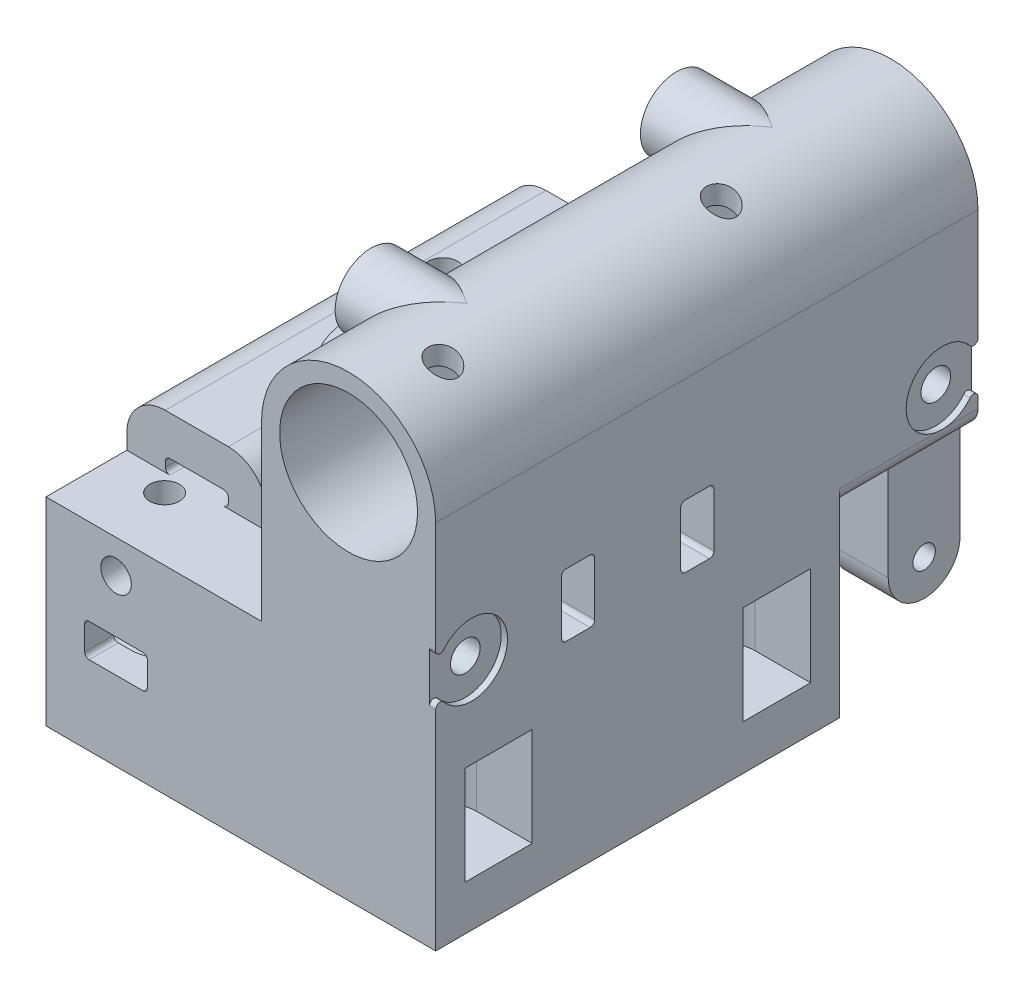
SolidWorks part; units mm, degrees
ref_plane "Front Plane" through (0, 0, 0) normal (0, 0, 1) x (1, 0, 0)
ref_plane "Top Plane" through (0, 0, 0) normal (0, 1, 0) x (1, 0, 0)
ref_plane "Right Plane" through (0, 0, 0) normal (1, 0, 0) x (0, 0, -1)
sketch "Sketch1" plane through (0, 0, 0) normal (0, 0, 1) x (1, 0, 0)
  line L57 (9.7, 0) -> (9.7, -41.3)
  line L58 (-9.7, -19.2) -> (-18.1, -19.2)
  line L61 (-29.4, -32) -> (-29.4, -29.3)
  line L62 (-29.4, -18.1) -> (-29.4, -18.7)
  line L63 (-28.9, -19.2) -> (-22.9, -19.2)
  line L64 (-22.4, -18.7) -> (-22.4, -18.1)
  line L65 (-22.9, -17.6) -> (-28.9, -17.6)
  line L66 (-28.9, -32.5) -> (-22.9, -32.5)
  line L67 (-22.4, -32) -> (-22.4, -29.3)
  line L68 (-28.9, -28.8) -> (-22.9, -28.8)
  line L76 (-9.7, -19.2) -> (-9.7, 0)
  line L77 (9.7, -41.3) -> (-33.7, -41.3)
  line L80 (-33.7, -41.3) -> (-33.7, -17.49)
  line L81 (-29.41, -13.2) -> (-22.39, -13.2)
  line L82 (-18.1, -17.49) -> (-18.1, -19.2)
  circle A0 centre (0, 0) radius 7.68
  arc A39 (9.7, 0) -> (-9.7, 0) centre (0, 0) ccw
  circle A59 centre (-25.9, -22.91) radius 1.7
  arc A60 (-28.9, -17.6) -> (-29.4, -18.1) centre (-28.9, -18.1) ccw
  arc A61 (-29.4, -18.7) -> (-28.9, -19.2) centre (-28.9, -18.7) ccw
  arc A62 (-22.9, -19.2) -> (-22.4, -18.7) centre (-22.9, -18.7) ccw
  arc A63 (-22.4, -18.1) -> (-22.9, -17.6) centre (-22.9, -18.1) ccw
  arc A64 (-29.4, -29.3) -> (-28.9, -28.8) centre (-28.9, -29.3) cw
  arc A65 (-22.4, -29.3) -> (-22.9, -28.8) centre (-22.9, -29.3) ccw
  arc A66 (-22.9, -32.5) -> (-22.4, -32) centre (-22.9, -32) ccw
  arc A67 (-29.4, -32) -> (-28.9, -32.5) centre (-28.9, -32) ccw
  arc A70 (-29.41, -13.2) -> (-33.7, -17.49) centre (-29.41, -17.49) ccw
  arc A71 (-18.1, -17.49) -> (-22.39, -13.2) centre (-22.39, -17.49) ccw
extrude "Boss-Extrude1" add sketch "Sketch1" along normal blind 60.4
sketch "Sketch8" plane through (0, -41.3, 0) normal (0, 1, 0) x (1, 0, 0)
  line L6 (-12, -48.01) -> (-7.68, -48.01)
  line L8 (-12, -27.79) -> (-7.68, -27.79)
  line L9 (-7.68, -48.01) -> (-7.68, -27.79)
  arc A1 (-12, -27.79) -> (-12, -48.01) centre (-12, -37.9) ccw
extrude "Boss-Extrude3" add sketch "Sketch8" along normal blind 34.02
sketch "Sketch2" plane through (0, 0, 0) normal (0, 0, -1) x (-1, 0, 0)
  line L0 (22.39, -15.34) -> (29.41, -15.34)
  line L1 (20.24, -17.49) -> (20.24, -24.62)
  line L2 (22.39, -26.77) -> (29.41, -26.77)
  line L3 (31.56, -17.49) -> (31.56, -24.62)
  arc A1 (22.39, -15.34) -> (20.24, -17.49) centre (22.39, -17.49) ccw
  arc A2 (31.56, -17.49) -> (29.41, -15.34) centre (29.41, -17.49) ccw
  arc A3 (29.41, -26.77) -> (31.56, -24.62) centre (29.41, -24.62) ccw
  arc A4 (20.24, -24.62) -> (22.39, -26.77) centre (22.39, -24.62) ccw
sketch "Sketch3" plane through (9.7, 0, 0) normal (1, 0, 0) x (0, 0, -1)
  line L11 (-46.39, -12.2) -> (-46.39, -18.2)
  line L12 (-43.19, -18.7) -> (-45.89, -18.7)
  line L13 (-42.69, -12.2) -> (-42.69, -18.2)
  line L14 (-43.19, -11.7) -> (-45.89, -11.7)
  line L15 (-33.11, -12.2) -> (-33.11, -18.2)
  line L16 (-29.91, -18.7) -> (-32.61, -18.7)
  line L17 (-29.41, -12.2) -> (-29.41, -18.2)
  line L18 (-29.91, -11.7) -> (-32.61, -11.7)
  circle A10 centre (-4, -15.2) radius 1.65
  circle A11 centre (-56.4, -15.2) radius 1.65
  arc A12 (-29.91, -11.7) -> (-29.41, -12.2) centre (-29.91, -12.2) cw
  arc A13 (-29.41, -18.2) -> (-29.91, -18.7) centre (-29.91, -18.2) cw
  arc A14 (-32.61, -18.7) -> (-33.11, -18.2) centre (-32.61, -18.2) cw
  arc A15 (-32.61, -11.7) -> (-33.11, -12.2) centre (-32.61, -12.2) ccw
  arc A16 (-43.19, -11.7) -> (-42.69, -12.2) centre (-43.19, -12.2) cw
  arc A17 (-42.69, -18.2) -> (-43.19, -18.7) centre (-43.19, -18.2) cw
  arc A18 (-45.89, -18.7) -> (-46.39, -18.2) centre (-45.89, -18.2) cw
  arc A19 (-45.89, -11.7) -> (-46.39, -12.2) centre (-45.89, -12.2) ccw
sketch "Sketch4" plane through (0, -41.3, 0) normal (0, -1, 0) x (1, 0, 0)
  circle A0 centre (-12, 37.9) radius 8.49
extrude "Cut-Extrude1" cut sketch "Sketch4" against normal blind 32
sketch "Sketch6" plane through (0, -41.3, 0) normal (0, -1, 0) x (1, 0, 0)
  circle A1 centre (3.5, 53.4) radius 1.65
  circle A2 centre (-27.5, 53.4) radius 1.65
  circle A3 centre (-27.5, 22.4) radius 1.65
  circle A4 centre (3.5, 22.4) radius 1.65
extrude "Cut-Extrude2" cut sketch "Sketch2" against normal blind 30.2
extrude "Cut-Extrude4" cut sketch "Sketch3" against normal up to next
sketch "Sketch9" plane through (9.7, 0, 0) normal (1, 0, 0) x (0, 0, -1)
  line L0 (-60.4, -12.3716) -> (-60.4, -18.0284)
  line L1 (0, -12.3716) -> (0, -18.0284)
  arc A0 (-60.4, -12.3716) -> (-59.5111, -12.6858) centre (-59.9, -12.3716) ccw
  arc A1 (-59.5111, -17.7142) -> (-59.5111, -12.6858) centre (-56.4, -15.2) ccw
  arc A2 (-59.5111, -17.7142) -> (-60.4, -18.0284) centre (-59.9, -18.0284) ccw
  arc A3 (-0.8889, -17.7142) -> (0, -18.0284) centre (-0.5, -18.0284) cw
  arc A4 (-0.8889, -17.7142) -> (-0.8889, -12.6858) centre (-4, -15.2) cw
  arc A5 (0, -12.3716) -> (-0.8889, -12.6858) centre (-0.5, -12.3716) cw
extrude "Cut-Extrude5" cut sketch "Sketch9" against normal blind 0.7
sketch "Sketch10" plane through (-9.7, 0, 0) normal (-1, 0, 0) x (0, 0, 1)
  circle A0 centre (4, -15.2) radius 3.6
  circle A1 centre (56.4, -15.2) radius 3.6
extrude "Cut-Extrude6" cut sketch "Sketch10" against normal blind 2
sketch "Sketch14" plane through (0, 0, 0) normal (0, 0, -1) x (-1, 0, 0)
  line L3 (-9.7, -19.2) -> (-9.7, -41.3)
  line L5 (-7.7, -21.2) -> (7.7, -21.2)
  line L8 (9.7, -19.2) -> (18.1, -19.2)
  line L11 (18.1, -19.2) -> (18.1, -24.62)
  line L12 (-9.7, -41.3) -> (33.7, -41.3)
  line L15 (33.7, -41.3) -> (33.7, -24.62)
  line L17 (22.39, -28.91) -> (29.41, -28.91)
  arc A2 (-9.7, -19.2) -> (-7.7, -21.2) centre (-7.7, -19.2) ccw
  arc A3 (7.7, -21.2) -> (9.7, -19.2) centre (7.7, -19.2) ccw
  arc A8 (18.1, -24.62) -> (22.39, -28.91) centre (22.39, -24.62) ccw
  arc A9 (29.41, -28.91) -> (33.7, -24.62) centre (29.41, -24.62) ccw
sketch "Sketch15" plane through (0, 0, 0) normal (0, 0, -1) x (-1, 0, 0)
  line L1 (22.39, -13.2) -> (29.41, -13.2)
  line L3 (22.39, -28.91) -> (29.41, -28.91)
  line L12 (18.1, -17.49) -> (18.1, -24.62)
  line L14 (33.7, -17.49) -> (33.7, -24.62)
  arc A4 (22.39, -13.2) -> (18.1, -17.49) centre (22.39, -17.49) ccw
  arc A5 (33.7, -17.49) -> (29.41, -13.2) centre (29.41, -17.49) ccw
  arc A9 (29.41, -28.91) -> (33.7, -24.62) centre (29.41, -24.62) ccw
  arc A10 (18.1, -24.62) -> (22.39, -28.91) centre (22.39, -24.62) ccw
extrude "Cut-Extrude8" cut sketch "Sketch14" against normal blind 15.4
extrude "Cut-Extrude9" cut sketch "Sketch15" against normal blind 9
extrude "Cut-Extrude10" cut sketch "Sketch6" against normal through all
sketch "Sketch16" plane through (0, -41.3, 0) normal (0, -1, 0) x (1, 0, 0)
  circle A0 centre (-12, 37.9) radius 11.5
extrude "Cut-Extrude11" cut sketch "Sketch16" against normal blind 2.5
sketch "Sketch17" plane through (0, 0, 60.4) normal (0, 0, 1) x (1, 0, 0)
  line L3 (-29.41, -13.2) -> (-22.39, -13.2)
  line L6 (-33.7, -17.49) -> (-33.7, -19.2)
  line L7 (-33.7, -19.2) -> (-18.1, -19.2)
  line L8 (-18.1, -17.49) -> (-18.1, -19.2)
  arc A5 (-18.1, -17.49) -> (-22.39, -13.2) centre (-22.39, -17.49) ccw
  arc A6 (-29.41, -13.2) -> (-33.7, -17.49) centre (-29.41, -17.49) ccw
extrude "Cut-Extrude12" cut sketch "Sketch17" against normal blind 9
sketch "Sketch12" plane through (0, -41.3, 0) normal (0, -1, 0) x (1, 0, 0)
  line L5 (-27.5, 49.65) -> (-33.7, 49.65)
  line L19 (-27.5, 57.15) -> (-33.7, 57.15)
  line L20 (-33.7, 49.65) -> (-33.7, 57.15)
  line L21 (3.5, 49.65) -> (9.7, 49.65)
  line L23 (3.5, 57.15) -> (9.7, 57.15)
  line L24 (9.7, 49.65) -> (9.7, 57.15)
  line L25 (3.5, 18.65) -> (9.7, 18.65)
  line L27 (3.5, 26.15) -> (9.7, 26.15)
  line L28 (9.7, 18.65) -> (9.7, 26.15)
  circle A5 centre (-27.5, 22.4) radius 3.75
  arc A6 (-27.5, 49.65) -> (-27.5, 57.15) centre (-27.5, 53.4) ccw
  arc A7 (3.5, 57.15) -> (3.5, 49.65) centre (3.5, 53.4) ccw
  arc A8 (3.5, 26.15) -> (3.5, 18.65) centre (3.5, 22.4) ccw
extrude "Cut-Extrude13" cut sketch "Sketch12" against normal blind 11 from offset 5 offset against normal yes
sketch "Sketch20" plane through (-9.7, 0, 0) normal (-1, 0, 0) x (0, 0, 1)
  circle A0 centre (13.2, 5.7) radius 4
  circle A1 centre (47.2, 5.7) radius 4
extrude "Boss-Extrude4" add sketch "Sketch20" against normal up to surface and the other way blind 1 up to face at (3.0891, 9.195, 23.998)
sketch "Sketch19" plane through (-10.7, 0, 0) normal (-1, 0, 0) x (0, 0, 1)
  circle A0 centre (13.2, 5.7) radius 1.65
  circle A1 centre (47.2, 5.7) radius 1.65
extrude "Cut-Extrude14" cut sketch "Sketch19" against normal up to next
sketch "Sketch21" plane through (9.7, 0, 0) normal (1, 0, 0) x (0, 0, -1)
  line L7 (-8, -32.5) -> (-8, -21.2)
  line L8 (-8, -21.2) -> (0, -21.2)
  line L9 (0, -32.5) -> (0, -21.2)
  circle A0 centre (-4, -32.5) radius 1.25
  arc A1 (-8, -32.5) -> (0, -32.5) centre (-4, -32.5) ccw
extrude "Boss-Extrude5" add sketch "Sketch21" against normal blind 6 from vertex starting at point (7.7, -21.2, 0)
sketch "Sketch22" plane through (0, 0, 30.2) normal (0, 0, -1) x (-1, 0, 0)
  line L0 (22.9, -16.9) -> (28.9, -16.9)
  line L1 (22.4, -17.4) -> (22.4, -18.7)
  line L2 (22.9, -19.2) -> (28.9, -19.2)
  line L3 (29.4, -17.4) -> (29.4, -18.7)
  arc A0 (28.9, -19.2) -> (29.4, -18.7) centre (28.9, -18.7) ccw
  arc A1 (29.4, -17.4) -> (28.9, -16.9) centre (28.9, -17.4) ccw
  arc A2 (22.9, -16.9) -> (22.4, -17.4) centre (22.9, -17.4) ccw
  arc A3 (22.9, -19.2) -> (22.4, -18.7) centre (22.9, -18.7) cw
extrude "Cut-Extrude15" cut sketch "Sketch22" against normal blind 8
